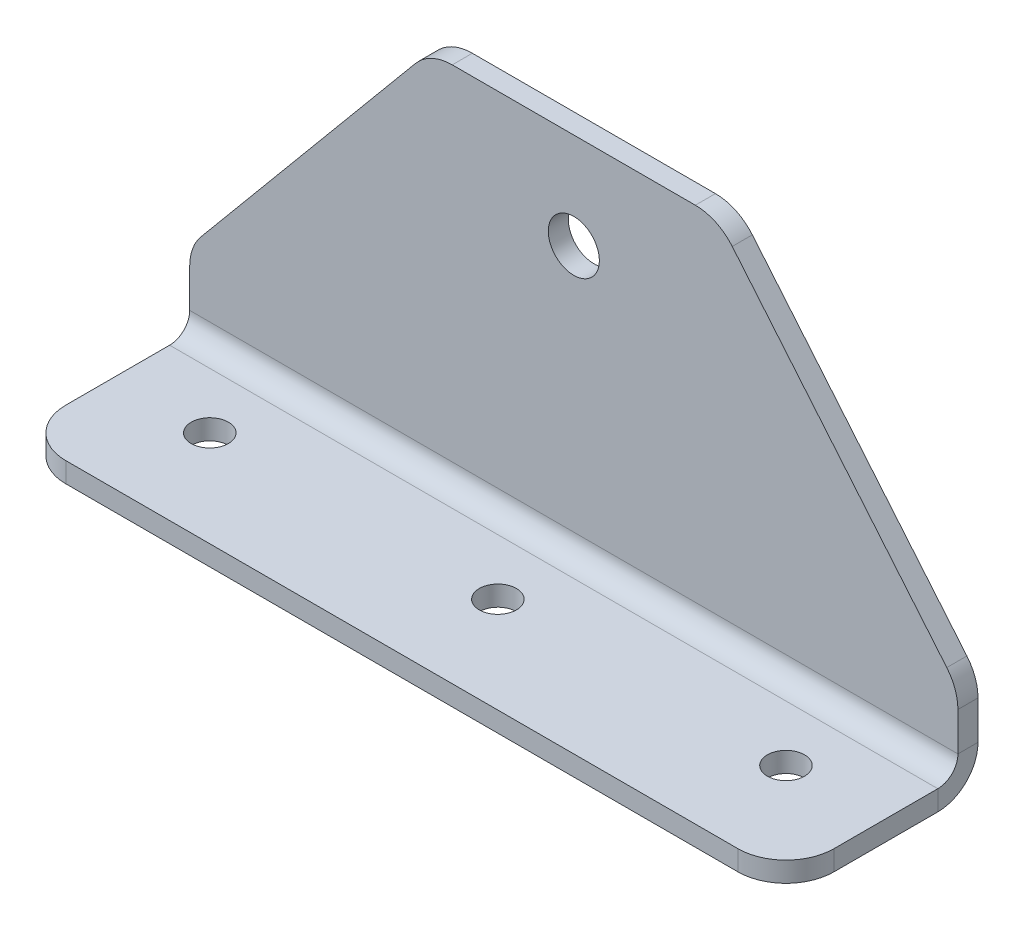
SolidWorks part; units mm, degrees
note: The reader was unsure of these and kept them because the rebuilt part matched: thickness of "Base-Flange1", "Edge-Flange1", "Sheet-Metal1", "Sheet-Metal2", "Sheet-Metal3", "Sheet-Metal4"; flange length of "Edge-Flange1".
material "Plain Carbon Steel"
ref_plane "Front Plane" through (0, 0, 0) normal (0, 0, 1) x (1, 0, 0)
ref_plane "Top Plane" through (0, 0, 0) normal (0, 1, 0) x (1, 0, 0)
ref_plane "Right Plane" through (0, 0, 0) normal (1, 0, 0) x (0, 0, -1)
sketch "Sketch1" plane through (0, 0, 0) normal (0, 0, 1) x (1, 0, 0)
  line L0 (0, 0) -> (0, 12.7)
  line L1 (31.75, 50.8) -> (69.85, 50.8)
  line L2 (69.85, 50.8) -> (101.6, 12.7)
  line L3 (101.6, 12.7) -> (101.6, 0)
  line L4 (101.6, 0) -> (0, 0)
  line L5 (0, 12.7) -> (31.75, 50.8)
  dimension "D1" = 50.8
  dimension "D2" = 101.6
  dimension "D3" = 12.7
  dimension "D4" = 31.75
base flange "Base-Flange1" sketch "Sketch1" thickness 2.6568 reverse thickness direction no parameters "D1"=2.6568
edge flange "Edge-Flange1" sketch "Sketch8" flange angle 90 flange length 25.4 flange position material inside bend radius 2.6568 thickness 2.6568 relief rectangular parameters "D1"=3.0378, "D6"=10
sketch "Sketch8" plane through (0, 0, 0) normal (0, 1, 0) x (-1, 0, 0)
  line L2 (-101.6, 0) -> (-101.6, 22.7432)
  line L3 (-101.6, 22.7432) -> (0, 22.7432)
  line L4 (0, 22.7432) -> (0, 0)
  line L5 (0, 0) -> (-101.6, 0) construction
  line L6 (0, 0) -> (-101.6, 0)
bend "EdgeBend1" bend radius 2.6568 bend angle 90 parameters "D5"=1
fillet "Fillet1" radius 6.35 6 edges at (0, 1.3284, 22.7432) (101.6, 1.3284, 22.7432) (101.6, 12.7, -1.3284) (69.85, 50.8, -1.3284) (31.75, 50.8, -1.3284) (0, 12.7, -1.3284)
hole_wizard "#10 (0.1935) Diameter Hole1" positions "Sketch9" profile "Sketch10" hole size "#10" standard "ANSI Inch" end condition through all
sketch "Sketch9" plane through (0, 0, 0) normal (0, -1, 0) x (-1, 0, 0)
  line L0 (-101.6, 2.6568) -> (0, 2.6568) construction
  line L1 (0, -2.6568) -> (0, -16.3932) construction
  point P0 (-88.9, -10.0432)
  point P2 (-50.8, -10.0432)
  point P4 (-12.7, -10.0432)
  dimension "D1" = 12.7
  dimension "D2" = 12.7
  dimension "D3" = 50.8
  dimension "D4" = 88.9
sketch "Sketch10" plane through (88.9, 0, 10.0432) normal (1, 0, 0) x (0, 0, -1)
  line L0 (0, 0) -> (0, 50.8)
  line L1 (0, 50.8) -> (2.4574, 50.8)
  line L2 (2.4574, 50.8) -> (2.4574, 0)
  line L5 (2.4574, 0) -> (0, 0)
  line L11 (0, -6.35) -> (0, 107.95) construction
  dimension "Thru Hole Dia." = 4.9149
  dimension "Thru Hole Depth" = 50.8
hole_wizard "1/4 Clearance Hole1" positions "Sketch11" profile "Sketch12" hole size "1/4" standard "ANSI Inch" end condition through all
sketch "Sketch11" plane through (0, 0, 0) normal (0, 0, 1) x (1, 0, 0)
  line L0 (6.35, 0) -> (95.25, 0) construction
  point P0 (50.8, 38.1)
  dimension "D1" = 50.8
  dimension "D2" = 38.1
sketch "Sketch12" plane through (50.8, 38.1, 0) normal (1, 0, 0) x (0, -1, 0)
  line L0 (0, 0) -> (0, 2.6568)
  line L1 (0, 2.6568) -> (3.3782, 2.6568)
  line L2 (3.3782, 2.6568) -> (3.3782, 0)
  line L5 (3.3782, 0) -> (0, 0)
  line L11 (0, -6.35) -> (0, 107.95) construction
  dimension "Thru Hole Dia." = 6.7564
  dimension "Thru Hole Depth" = 2.6568
sketch "Bend-Lines1" [suppressed] plane through (0, 0, 0) normal (0, 1, 0) x (1, 0, 0)
sketch "Bounding-Box1" [suppressed] plane through (0, 0, 0) normal (0, 1, 0) x (1, 0, 0)
sheet metal parameters "Sheet-Metal1" thickness 2.6568 parameters "D1"=3.0378, "D7"=3.0378
flat pattern "Flat-Pattern1" [suppressed]
sketch "Bend-Lines2" plane through (0, 0, 0) normal (0, 1, 0) x (1, 0, 0)
sketch3d "Bounding-Box2" [suppressed]
  line L0 (0, 0, 0) -> (-76.2, 0, 0) construction
  line L1 (0, 50.8, 0) -> (-76.2, 50.8, 0) construction
  line L2 (0, 0, 0) -> (0, 50.8, 0) construction
  line L3 (-76.2, 0, 0) -> (-76.2, 50.8, 0) construction
sheet metal parameters "Sheet-Metal2" thickness 2.6568 parameters "D1"=3.0378, "D7"=3.4163
flat pattern "Flat-Pattern1"
sketch "Bend-Lines2" plane through (0, 0, 0) normal (0, 0, 1) x (1, 0, 0)
  line L0 (0, 2.2328) -> (101.6, 2.2328) construction
  line L1 (0, 2.2328) -> (101.6, 2.2328) construction
sketch3d "Bounding-Box2" [suppressed]
  line L0 (0, 50.8, 0) -> (101.6, 50.8, 0) construction
  line L1 (0, -20.9344, 0) -> (101.6, -20.9344, 0) construction
  line L2 (0, 50.8, 0) -> (0, -20.9344, 0) construction
  line L3 (101.6, 50.8, 0) -> (101.6, -20.9344, 0) construction
bend of the flat pattern "Flatten-<EdgeBend1>1"
sheet metal parameters "Sheet-Metal3" thickness 2.6568 parameters "D1"=3.0378, "D7"=3.4163
flat pattern "Flat-Pattern1"
sketch "Bend-Lines2" plane through (0, 0, 0) normal (0, 0, 1) x (1, 0, 0)
  line L0 (0, 2.2328) -> (101.6, 2.2328) construction
  line L1 (0, 2.2328) -> (101.6, 2.2328) construction
sketch3d "Bounding-Box2" [suppressed]
  line L0 (0, 50.8, 0) -> (101.6, 50.8, 0) construction
  line L1 (0, -20.9344, 0) -> (101.6, -20.9344, 0) construction
  line L2 (0, 50.8, 0) -> (0, -20.9344, 0) construction
  line L3 (101.6, 50.8, 0) -> (101.6, -20.9344, 0) construction
bend of the flat pattern "Flatten-<EdgeBend1>1"
sheet metal parameters "Sheet-Metal4" thickness 2.6568 parameters "D1"=3.0378, "D7"=3.4163
flat pattern "Flat-Pattern1"
sketch "Bend-Lines2" plane through (0, 0, 0) normal (0, 0, 1) x (1, 0, 0)
  line L0 (0, 2.1837) -> (101.6, 2.1837) construction
  line L1 (0, 2.1837) -> (101.6, 2.1837) construction
sketch3d "Bounding-Box2" [suppressed]
  line L0 (0, 50.8, 0) -> (101.6, 50.8, 0) construction
  line L1 (0, -21.0327, 0) -> (101.6, -21.0327, 0) construction
  line L2 (0, 50.8, 0) -> (0, -21.0327, 0) construction
  line L3 (101.6, 50.8, 0) -> (101.6, -21.0327, 0) construction
bend of the flat pattern "Flatten-<EdgeBend1>1"
